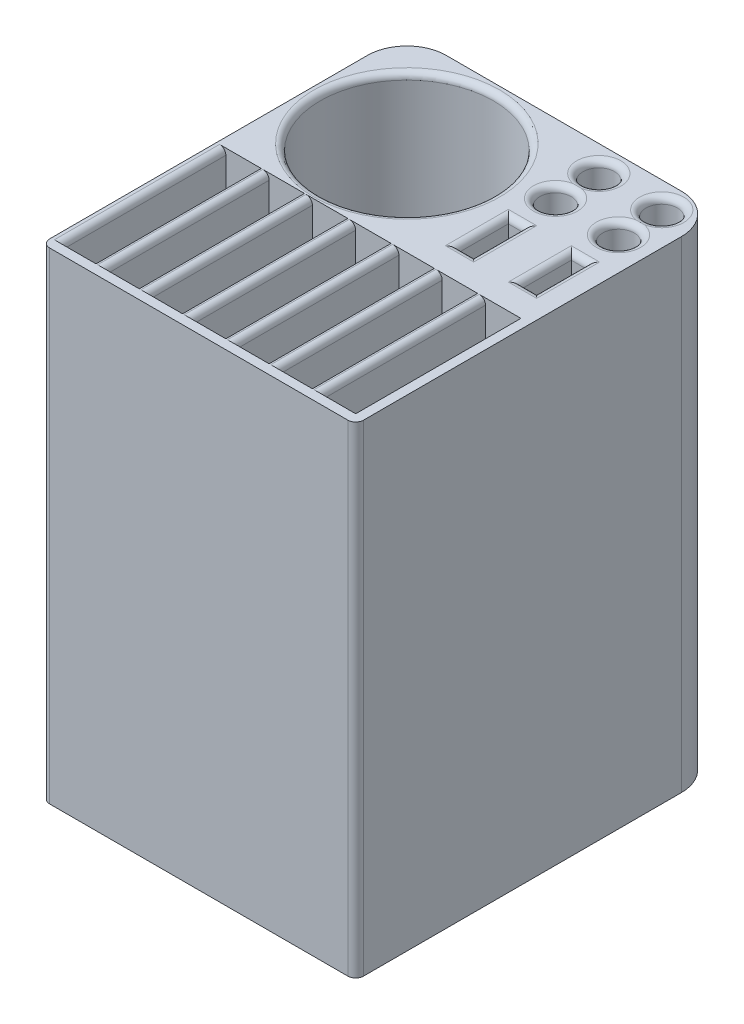
SolidWorks part; units mm, degrees
ref_plane "前视基准面" through (0, 0, 0) normal (0, 0, 1) x (1, 0, 0)
ref_plane "上视基准面" through (0, 0, 0) normal (0, 1, 0) x (1, 0, 0)
ref_plane "右视基准面" through (0, 0, 0) normal (1, 0, 0) x (0, 0, -1)
sketch "草图1" plane through (0, 0, 0) normal (0, 1, 0) x (1, 0, 0)
  line L0 (3.25, 10.5) -> (7.75, 10.5)
  line L5 (-2.25, 10.5) -> (2.25, 10.5)
  line L6 (-2.25, 10.5) -> (-2.25, -10.5)
  line L7 (-2.25, -10.5) -> (2.25, -10.5)
  line L8 (2.25, 10.5) -> (2.25, -10.5)
  line L9 (-2.25, 10.5) -> (2.25, -10.5) construction
  line L10 (-2.25, -10.5) -> (2.25, 10.5) construction
  line L11 (3.25, 10.5) -> (3.25, -10.5)
  line L12 (7.75, 10.5) -> (7.75, -10.5)
  line L13 (3.25, -10.5) -> (7.75, -10.5)
  line L14 (8.75, 10.5) -> (13.25, 10.5)
  line L15 (8.75, 10.5) -> (8.75, -10.5)
  line L16 (13.25, 10.5) -> (13.25, -10.5)
  line L17 (8.75, -10.5) -> (13.25, -10.5)
  line L18 (14.25, 10.5) -> (18.75, 10.5)
  line L19 (14.25, 10.5) -> (14.25, -10.5)
  line L20 (18.75, 10.5) -> (18.75, -10.5)
  line L21 (14.25, -10.5) -> (18.75, -10.5)
  line L22 (19.75, 10.5) -> (24.25, 10.5)
  line L23 (19.75, 10.5) -> (19.75, -10.5)
  line L24 (24.25, 10.5) -> (24.25, -10.5)
  line L25 (19.75, -10.5) -> (24.25, -10.5)
  line L26 (25.25, 10.5) -> (29.75, 10.5)
  line L27 (25.25, 10.5) -> (25.25, -10.5)
  line L28 (29.75, 10.5) -> (29.75, -10.5)
  line L29 (25.25, -10.5) -> (29.75, -10.5)
  line L31 (23.25, 20.9) -> (25.25, 20.9)
  line L32 (23.25, 20.9) -> (23.25, 14.5)
  line L33 (23.25, 14.5) -> (25.25, 14.5)
  line L34 (25.25, 20.9) -> (25.25, 14.5)
  line L38 (24.25, 25.9) -> (24.25, 20.9) construction
  line L39 (30.75, 10.5) -> (35.25, 10.5)
  line L40 (30.75, 10.5) -> (30.75, -10.5)
  line L41 (35.25, 10.5) -> (35.25, -10.5)
  line L42 (30.75, -10.5) -> (35.25, -10.5)
  line L43 (33.25, 20.9) -> (33.25, 14.5)
  line L44 (31.25, 20.9) -> (33.25, 20.9)
  line L45 (31.25, 20.9) -> (31.25, 14.5)
  line L46 (31.25, 14.5) -> (33.25, 14.5)
  line L48 (36.45, -11.7) -> (-3.45, -11.7)
  line L49 (36.45, -11.7) -> (36.45, 34.7)
  line L50 (36.45, 34.7) -> (-3.45, 34.7)
  line L51 (-3.45, -11.7) -> (-3.45, 34.7)
  circle A0 centre (8.75, 22.5) radius 11
  circle A1 centre (24.25, 25.9) radius 2
  circle A3 centre (32.25, 25.9) radius 2
  circle A4 centre (24.25, 31.4) radius 2
  circle A5 centre (32.25, 31.4) radius 2
  point P0 (0, 0)
  point P1 (0, 0)
  dimension "D4" = 22
  dimension "D5" = 12
  dimension "D6" = 11
  dimension "D12" = 4
  dimension "D13" = 2
  dimension "D14" = 6
  dimension "D15" = 1.2
  dimension "D16" = 5
  dimension "D20" = 8
  dimension "D1" = 4.5
  dimension "D2" = 21
  dimension "D7" = 6.4
  dimension "D8" = 2
  dimension "D9" = 14.5
  dimension "D10" = 4
  dimension "D17" = 1.2
  dimension "D18" = 1.2
  dimension "D19" = 12.2
  dimension "D3" = 7
  dimension "D11" = 2
  dimension "D21" = 2
extrude "凸台-拉伸1" add sketch "草图1" along normal blind 60
sketch "草图2" plane through (0, 0, 0) normal (0, -1, 0) x (1, 0, 0)
  line L4 (36.45, -34.7) -> (36.45, 11.7)
  line L5 (36.45, 11.7) -> (-3.45, 11.7)
  line L6 (-3.45, 11.7) -> (-3.45, -34.7)
  line L7 (-3.45, -34.7) -> (36.45, -34.7)
  line L8 (36.45, -34.7) -> (36.45, 11.7)
  line L9 (36.45, 11.7) -> (-3.45, 11.7)
  line L10 (-3.45, 11.7) -> (-3.45, -34.7)
  line L11 (-3.45, -34.7) -> (36.45, -34.7)
  dimension "D1" = 0
extrude "凸台-拉伸2" add sketch "草图2" along normal blind 1.2
fillet "圆角1" radius 1 2 edges at (-3.45, 29.4, 11.7) (36.45, 29.4, 11.7)
fillet "圆角2" radius 5 2 edges at (-3.45, 29.4, -34.7) (36.45, 29.4, -34.7)
fillet "圆角3" radius 0.8 20 edges at (-2.25, 60, 0) (3.25, 60, 0) (8.75, 60, 0) (14.25, 60, 0) (19.75, 60, 0) (25.25, 60, 0) (30.75, 60, 0) (32.25, 60, -29.4) (24.25, 60, -29.4) (24.25, 60, -23.9) (32.25, 60, -23.9) (32.25, 60, -20.9) (32.25, 60, -14.5) (33.25, 60, -17.7) (31.25, 60, -17.7) (24.25, 60, -20.9) (23.25, 60, -17.7) (24.25, 60, -14.5) (25.25, 60, -17.7) (8.75, 60, -11.5)
